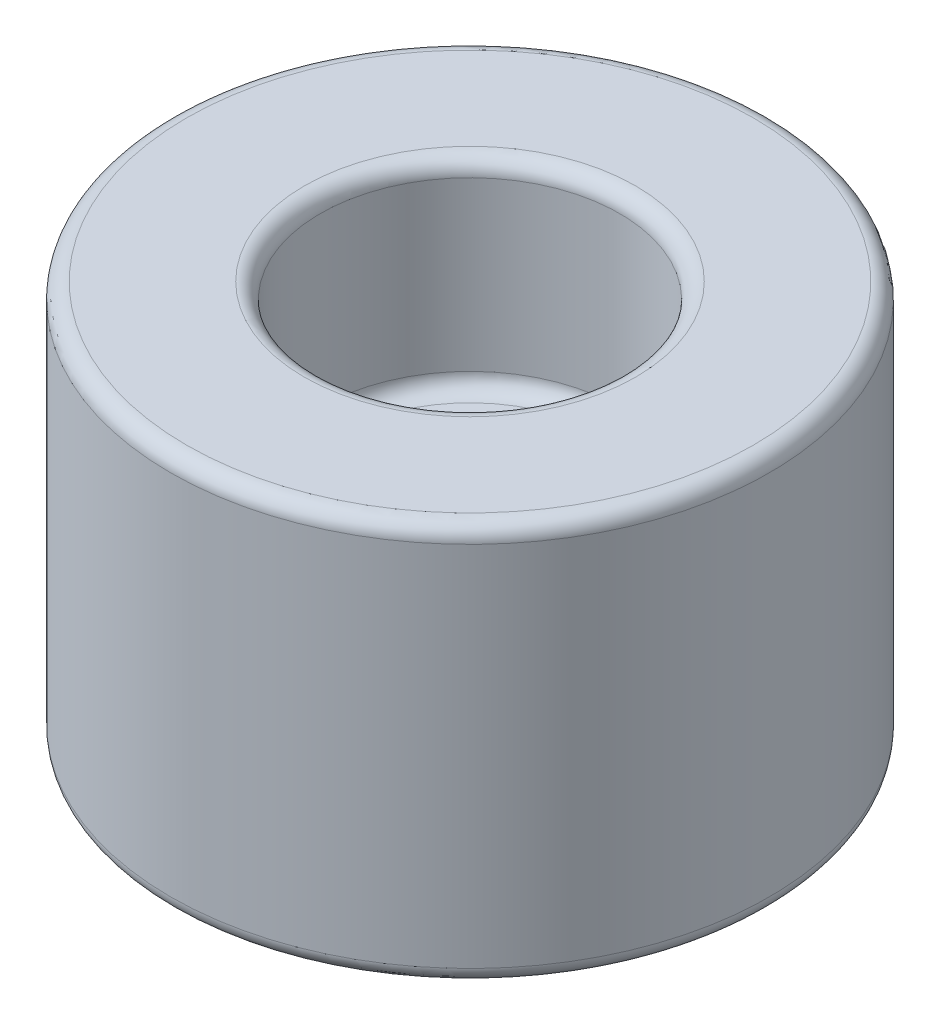
SolidWorks part; units mm, degrees
material "SBR"
ref_plane "Front Plane" through (0, 0, 0) normal (0, 0, 1) x (1, 0, 0)
ref_plane "Top Plane" through (0, 0, 0) normal (0, 1, 0) x (1, 0, 0)
ref_plane "Right Plane" through (0, 0, 0) normal (1, 0, 0) x (0, 0, -1)
sketch "Sketch1" plane through (0, 0, 0) normal (1, 0, 0) x (0, 0, -1)
  line L0 (0, 0) -> (0, 6.35) construction
  line L1 (1.7859, 6.35) -> (4.7625, 6.35)
  line L2 (4.7625, 6.35) -> (4.7625, 12.7)
  line L3 (4.7625, 12.7) -> (9.525, 12.7)
  line L4 (9.525, 12.7) -> (9.525, 0)
  line L5 (9.525, 0) -> (1.7859, 0)
  line L6 (1.7859, 6.35) -> (1.7859, 0)
  line L7 (1.7859, 0) -> (0, 0) construction
  dimension "D1" = 19.05
  dimension "D2" = 9.525
  dimension "D3" = 6.35
  dimension "D4" = 12.7
  dimension "D5" = 3.5719
revolve "Revolve1" add sketch "Sketch1" angle 360 about L0
fillet "Fillet1" radius 0.508 6 edges at (0, 0, -1.7859) (0, 6.35, -1.7859) (0, 6.35, -4.7625) (0, 12.7, -4.7625) (0, 0, -9.525) (0, 12.7, -9.525)
ref_plane "Contact Plane" through (0, 0, -9.525) normal (0, 0, -1) x (-1, 0, 0)
